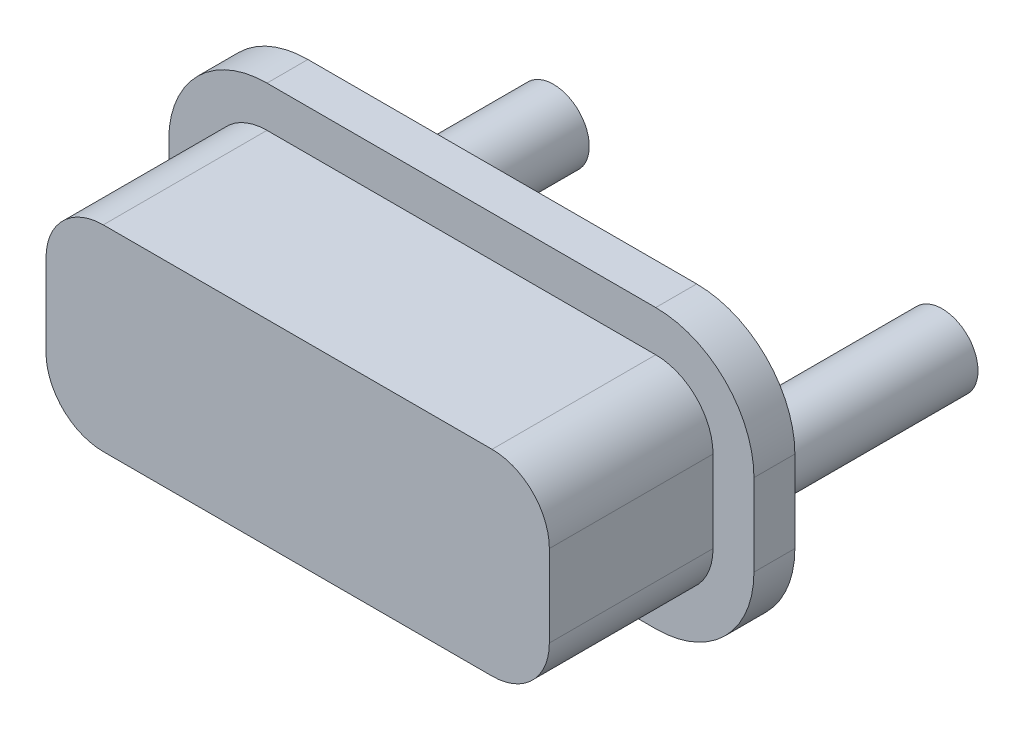
SolidWorks part; units mm, degrees
ref_plane "Front Plane" through (0, 0, 0) normal (0, 0, 1) x (1, 0, 0)
ref_plane "Top Plane" through (0, 0, 0) normal (0, 1, 0) x (1, 0, 0)
ref_plane "Right Plane" through (0, 0, 0) normal (1, 0, 0) x (0, 0, -1)
sketch "Sketch1" plane through (0, 0, 0) normal (0, 0, 1) x (1, 0, 0)
  line L24 (12.3, 57.365) -> (12.3, 61.365)
  line L25 (9.5, 64.165) -> (-9.5, 64.165)
  line L26 (-12.3, 61.365) -> (-12.3, 57.365)
  line L27 (-9.5, 54.565) -> (9.5, 54.565)
  line L28 (12.3, 57.365) -> (12.3, 61.365)
  line L29 (9.5, 64.165) -> (-9.5, 64.165)
  line L30 (-12.3, 61.365) -> (-12.3, 57.365)
  line L31 (-9.5, 54.565) -> (9.5, 54.565)
  arc A20 (9.5, 54.565) -> (12.3, 57.365) centre (9.5, 57.365) ccw
  arc A21 (12.3, 61.365) -> (9.5, 64.165) centre (9.5, 61.365) ccw
  arc A22 (-9.5, 64.165) -> (-12.3, 61.365) centre (-9.5, 61.365) ccw
  arc A23 (-12.3, 57.365) -> (-9.5, 54.565) centre (-9.5, 57.365) ccw
  arc A24 (9.5, 54.565) -> (12.3, 57.365) centre (9.5, 57.365) ccw
  arc A25 (12.3, 61.365) -> (9.5, 64.165) centre (9.5, 61.365) ccw
  arc A26 (-9.5, 64.165) -> (-12.3, 61.365) centre (-9.5, 61.365) ccw
  arc A27 (-12.3, 57.365) -> (-9.5, 54.565) centre (-9.5, 57.365) ccw
  dimension "D1" = 0.2
extrude "Boss-Extrude1" add sketch "Sketch1" against normal blind 10
sketch "Sketch2" plane through (0, 0, 0) normal (0, 0, 1) x (1, 0, 0)
  line L8 (14.3, 57.365) -> (14.3, 61.365)
  line L9 (9.5, 66.165) -> (-9.5, 66.165)
  line L10 (-14.3, 61.365) -> (-14.3, 57.365)
  line L11 (-9.5, 52.565) -> (9.5, 52.565)
  line L12 (14.3, 57.365) -> (14.3, 61.365)
  line L13 (9.5, 66.165) -> (-9.5, 66.165)
  line L14 (-14.3, 61.365) -> (-14.3, 57.365)
  line L15 (-9.5, 52.565) -> (9.5, 52.565)
  arc A8 (9.5, 52.565) -> (14.3, 57.365) centre (9.5, 57.365) ccw
  arc A9 (14.3, 61.365) -> (9.5, 66.165) centre (9.5, 61.365) ccw
  arc A10 (-9.5, 66.165) -> (-14.3, 61.365) centre (-9.5, 61.365) ccw
  arc A11 (-14.3, 57.365) -> (-9.5, 52.565) centre (-9.5, 57.365) ccw
  arc A12 (9.5, 52.565) -> (14.3, 57.365) centre (9.5, 57.365) ccw
  arc A13 (14.3, 61.365) -> (9.5, 66.165) centre (9.5, 61.365) ccw
  arc A14 (-9.5, 66.165) -> (-14.3, 61.365) centre (-9.5, 61.365) ccw
  arc A15 (-14.3, 57.365) -> (-9.5, 52.565) centre (-9.5, 57.365) ccw
  dimension "D1" = 2
extrude "Boss-Extrude2" add sketch "Sketch2" along normal blind 2 from surface starting at face at (0, 59.365, -10)
sketch "Sketch3" plane through (0, 0, 0) normal (0, 0, 1) x (1, 0, 0)
  arc A0 (9.5, 54.565) -> (12.3, 57.365) centre (9.5, 57.365) ccw construction
  arc A1 (-12.3, 57.365) -> (-9.5, 54.565) centre (-9.5, 57.365) ccw construction
  arc A2 (9.5, 54.565) -> (12.3, 57.365) centre (9.5, 57.365) ccw construction
  arc A3 (-12.3, 57.365) -> (-9.5, 54.565) centre (-9.5, 57.365) ccw construction
  circle A4 centre (9.5, 57.365) radius 1.75
  circle A5 centre (-9.5, 57.365) radius 1.75
  dimension "D1" = 3.5
extrude "Boss-Extrude3" add sketch "Sketch3" against normal blind 12 from surface starting at face at (0, 59.365, -10)
chamfer "Chamfer1" distance 1 angle 45 2 edges at (11.25, 57.365, -10) (-7.75, 57.365, -10)
sketch "Sketch4" plane through (0, 0, 0) normal (0, 0, 1) x (1, 0, 0)
  circle A0 centre (-11.4799, 55.3851) radius 1.5
  arc A1 (-12.3, 57.365) -> (-9.5, 54.565) centre (-9.5, 57.365) ccw construction
  circle A2 centre (11.4799, 55.3851) radius 1.5
  arc A3 (9.5, 54.565) -> (12.3, 57.365) centre (9.5, 57.365) ccw construction
  dimension "D1" = 3
extrude "Boss-Extrude4" [suppressed] add sketch "Sketch4" against normal blind 10 from surface
